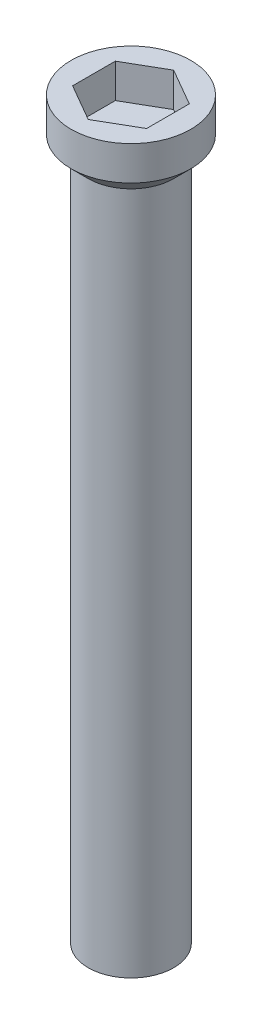
SolidWorks part; units mm, degrees
material "Cast Alloy Steel"
ref_plane "Front Plane" through (0, 0, 0) normal (0, 0, 1) x (1, 0, 0)
ref_plane "Top Plane" through (0, 0, 0) normal (0, 1, 0) x (1, 0, 0)
ref_plane "Right Plane" through (0, 0, 0) normal (1, 0, 0) x (0, 0, -1)
sketch "Sketch1" plane through (0, 0, 0) normal (0, 1, 0) x (1, 0, 0)
  circle A0 centre (0, 0) radius 2.5
  dimension "D1" = 5
extrude "Screw Length" add sketch "Sketch1" along normal blind 40
sketch "Sketch2" plane through (0, 40, 0) normal (0, 1, 0) x (1, 0, 0)
  circle A0 centre (0, 0) radius 3.5
  dimension "D1" = 7
extrude "Screw Cap" add sketch "Sketch2" along normal blind 3
sketch "Sketch3" plane through (0, 43, 0) normal (0, 1, 0) x (1, 0, 0)
  line L1 (0, 2.5) -> (-2.1651, 1.25)
  line L2 (-2.1651, 1.25) -> (-2.1651, -1.25)
  line L3 (-2.1651, -1.25) -> (0, -2.5)
  line L4 (0, -2.5) -> (2.1651, -1.25)
  line L5 (2.1651, -1.25) -> (2.1651, 1.25)
  line L6 (2.1651, 1.25) -> (0, 2.5)
  circle A0 centre (0, 0) radius 2.1651 construction
  dimension "D1" = 2.5
extrude "Screw Hole" cut sketch "Sketch3" against normal blind 2
chamfer "Chamfer1" distance 1 angle 45 1 edges at (0, 40, 3.5)
